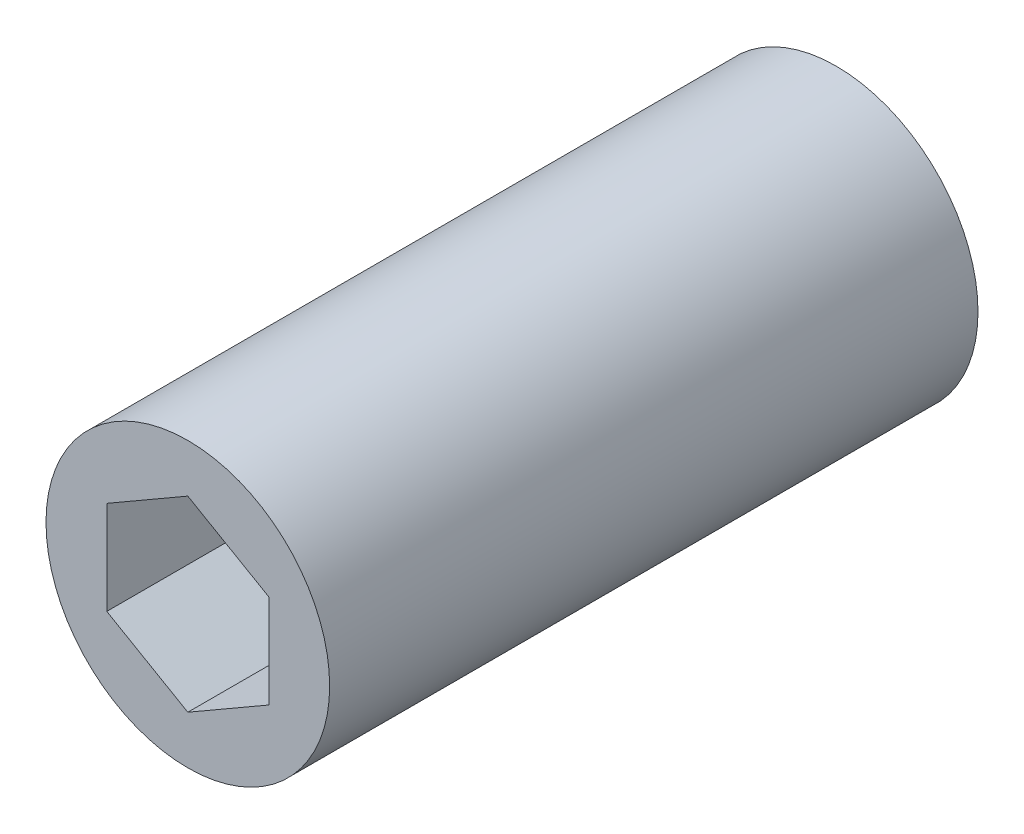
SolidWorks part; units mm, degrees
material "Nylon 101"
ref_plane "Front Plane" through (0, 0, 0) normal (0, 0, 1) x (1, 0, 0)
ref_plane "Top Plane" through (0, 0, 0) normal (0, 1, 0) x (1, 0, 0)
ref_plane "Right Plane" through (0, 0, 0) normal (1, 0, 0) x (0, 0, -1)
sketch "Sketch1" plane through (0, 0, 0) normal (0, 0, 1) x (1, 0, 0)
  line L1 (0, 7.3323) -> (-6.35, 3.6662)
  line L2 (-6.35, 3.6662) -> (-6.35, -3.6662)
  line L3 (-6.35, -3.6662) -> (0, -7.3323)
  line L4 (0, -7.3323) -> (6.35, -3.6662)
  line L5 (6.35, -3.6662) -> (6.35, 3.6662)
  line L6 (6.35, 3.6662) -> (0, 7.3323)
  circle A0 centre (0, 0) radius 11.1125
  circle A1 centre (0, 0) radius 6.35 construction
  dimension "D1" = 12.7
  dimension "D2" = 22.225
extrude "Boss-Extrude1" add sketch "Sketch1" along normal blind 50.8
